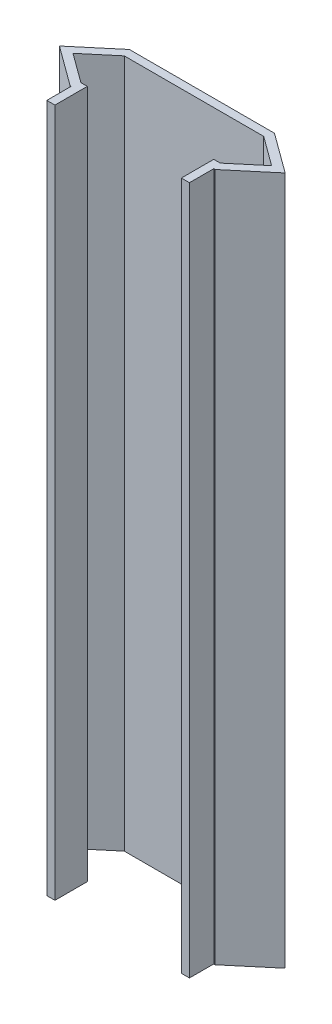
SolidWorks part; units mm, degrees
ref_plane "Front Plane" through (0, 0, 0) normal (0, 0, 1) x (1, 0, 0)
ref_plane "Top Plane" through (0, 0, 0) normal (0, 1, 0) x (1, 0, 0)
ref_plane "Right Plane" through (0, 0, 0) normal (1, 0, 0) x (0, 0, -1)
sketch "Sketch1" plane through (0, 0, 0) normal (0, 1, 0) x (1, 0, 0)
  line L9 (-5.8527, 1.9534) -> (11.3547, 1.9534)
  line L15 (11.3547, 1.9534) -> (14.972, -0.6901)
  line L16 (14.972, -0.6901) -> (11.5352, -3.5821)
  line L17 (11.5352, -3.5821) -> (10.7257, -3.5821)
  line L18 (10.7257, -3.5821) -> (10.7257, -6.5821)
  line L19 (-4.8743, -6.5821) -> (10.7257, -6.5821)
  line L20 (-4.8743, -3.5821) -> (-4.8743, -6.5821)
  line L21 (-4.8743, -3.5821) -> (-5.6722, -3.5821)
  line L22 (-5.6722, -3.5821) -> (-9.2895, -0.9387)
  line L23 (-9.2895, -0.9387) -> (-5.8527, 1.9534)
  line L24 (-6.2175, 2.9534) -> (11.6811, 2.9534)
  line L25 (11.6811, 2.9534) -> (16.591, -0.6346)
  line L26 (16.591, -0.6346) -> (11.8999, -4.5821)
  line L27 (11.8999, -4.5821) -> (11.7257, -4.5821)
  line L28 (11.7257, -4.5821) -> (11.7257, -7.5821)
  line L29 (-5.8743, -7.5821) -> (11.7257, -7.5821)
  line L30 (-5.8743, -4.5821) -> (-5.8743, -7.5821)
  line L31 (-5.8743, -4.5821) -> (-5.9987, -4.5821)
  line L32 (-5.9987, -4.5821) -> (-10.9085, -0.9941)
  line L33 (-10.9085, -0.9941) -> (-6.2175, 2.9534)
  line L34 (-4.8743, -6.5821) -> (-4.8743, -7.5821)
  line L35 (10.7257, -6.5821) -> (10.7257, -7.5821)
  dimension "D1" = 1
extrude "Boss-Extrude2" add sketch "Sketch1" along normal blind 85 contours L18 L35 L29 L28 L27 L26 L25 L24 L33 L32 L31 L30 L34 L20 L21 L22 L23 L9 L15 L16 L17 region at (-7.7607, 0, -0.7327)
